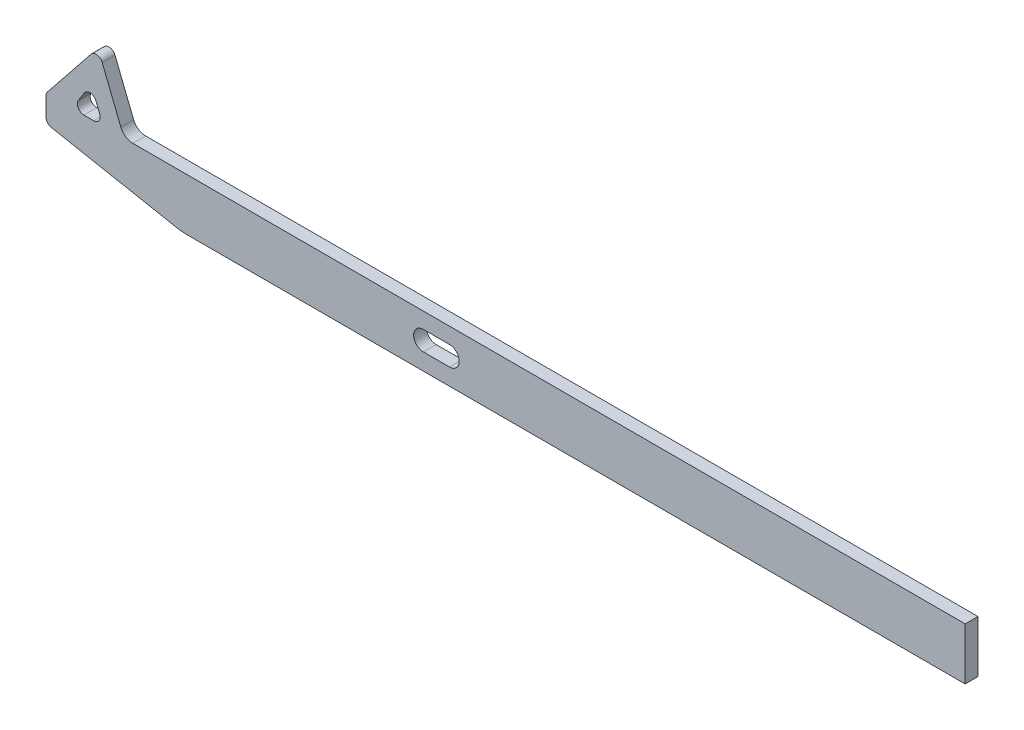
SolidWorks part; units mm, degrees
ref_plane "Front Plane" through (0, 0, 0) normal (0, 0, 1) x (1, 0, 0)
ref_plane "Top Plane" through (0, 0, 0) normal (0, 1, 0) x (1, 0, 0)
ref_plane "Right Plane" through (0, 0, 0) normal (1, 0, 0) x (0, 0, -1)
sketch "Sketch1" plane through (0, 0, 0) normal (0, 0, 1) x (1, 0, 0)
  line L0 (-110.4919, 6.2563) -> (-110.4919, 38.0063) construction
  line L1 (113.7998, -6.4437) -> (-77.3725, -6.4437)
  line L2 (113.7998, -6.4437) -> (113.7998, 6.2563)
  line L3 (113.7998, 6.2563) -> (-91.4419, 6.2563)
  line L4 (-97.7919, 22.1313) -> (-110.4919, 6.2563)
  line L5 (113.7998, -6.4437) -> (-110.4919, 6.2563) construction
  line L6 (113.7998, 6.2563) -> (-117.2068, -6.4437) construction
  line L7 (-110.4919, 38.0063) -> (-104.1419, 38.0063) construction
  line L8 (-110.4919, -0.0937) -> (-77.3725, -6.4437)
  line L9 (-104.1419, 38.0063) -> (-97.7919, 22.1313) construction
  line L10 (-104.1419, 6.2563) -> (-104.1419, 25.3063) construction
  line L11 (-104.1419, 25.3063) -> (-96.5219, 6.2563) construction
  line L12 (-104.1419, 6.2563) -> (-100.3319, 15.7813) construction
  line L13 (-100.3319, 15.7813) -> (-97.7919, 22.1313) construction
  line L14 (-110.4919, 6.2563) -> (-110.4919, -0.0937)
  line L15 (-97.7919, 22.1313) -> (-91.4419, 6.2563)
  line L16 (-104.1419, 6.2563) -> (-99.4608, 13.6034)
  line L17 (-99.4608, 13.6034) -> (-96.5219, 6.2563)
  line L18 (-96.5219, 6.2563) -> (-104.1419, 6.2563)
  line L19 (-97.7919, 22.1313) -> (-91.4419, 6.2563) construction
  point P0 (0, 0)
  dimension "D1" = 6.35
  dimension "D2" = 224.2918
  dimension "D3" = 6.35
  dimension "D5" = 31.75
  dimension "D6" = 19.05
  dimension "D7" = 6.35
  dimension "D9" = 12.7
extrude "Boss-Extrude1" add sketch "Sketch1" along normal blind 3.1242
fillet "Fillet4" radius 12.7 1 edges at (-77.3725, -6.4437, 1.5621)
fillet "Fillet8" radius 1.5875 6 edges at (-110.4919, -0.0937, 1.5621) (-110.4919, 6.2563, 1.5621) (-97.7919, 22.1313, 1.5621) (-99.4608, 13.6034, 1.5621) (-104.1419, 6.2563, 1.5621) (-96.5219, 6.2563, 1.5621)
fillet "Fillet9" radius 3.175 1 edges at (-91.4419, 6.2563, 1.5621)
sketch "Sketch2" plane through (0, 0, 3.1242) normal (0, 0, 1) x (1, 0, 0)
  line L0 (-18.4072, 0) -> (-12.0572, 0) construction
  line L1 (-18.4072, 2.3813) -> (-12.0572, 2.3813)
  line L2 (-18.4072, -2.3813) -> (-12.0572, -2.3813)
  line L4 (113.7998, -6.4437) -> (113.7998, 6.2563) construction
  arc A0 (-18.4072, 2.3813) -> (-18.4072, -2.3813) centre (-18.4072, 0) ccw
  arc A1 (-12.0572, -2.3813) -> (-12.0572, 2.3813) centre (-12.0572, 0) ccw
  point P3 (-15.2322, 0)
  point P8 (113.7998, -0.0937)
  dimension "D2" = 2.3813
  dimension "D1" = 6.35
  dimension "D3" = 129.032
extrude "Cut-Extrude1" cut sketch "Sketch2" against normal through all
